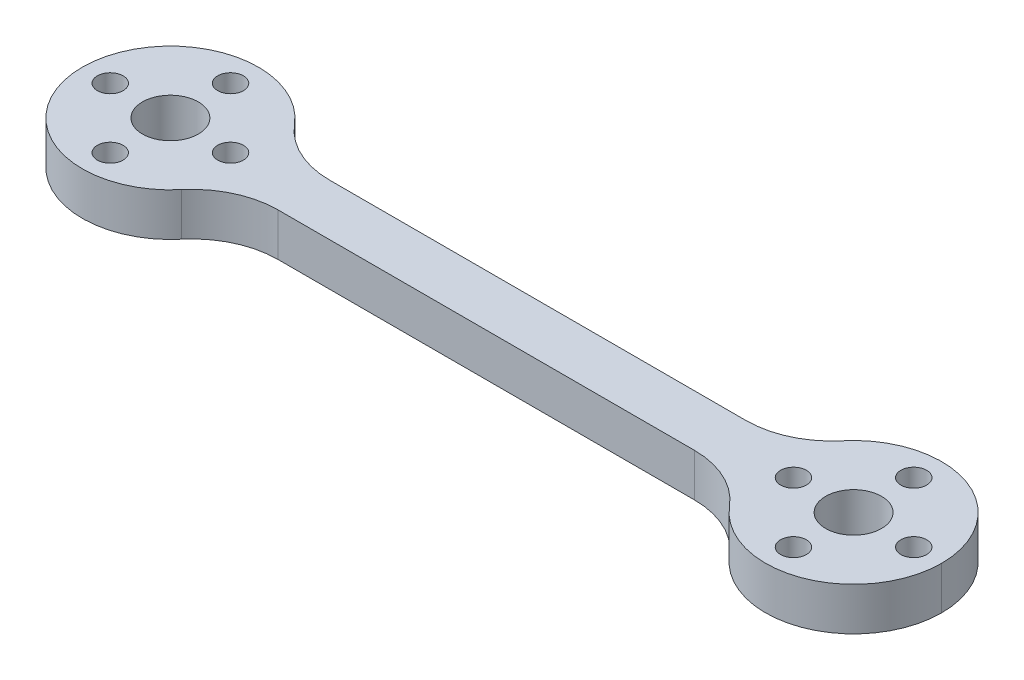
SolidWorks part; units mm, degrees
ref_plane "Front Plane" through (0, 0, 0) normal (0, 0, 1) x (1, 0, 0)
ref_plane "Top Plane" through (0, 0, 0) normal (0, 1, 0) x (1, 0, 0)
ref_plane "Right Plane" through (0, 0, 0) normal (1, 0, 0) x (0, 0, -1)
sketch "Sketch1" plane through (0, 0, 0) normal (0, 1, 0) x (1, 0, 0)
  line L0 (0, 10.25) -> (100, 10.25) construction
  line L1 (0, 0) -> (100, 0)
  line L2 (0, 0) -> (0, 20.5)
  line L3 (0, 20.5) -> (100, 20.5)
  line L4 (100, 0) -> (100, 20.5)
  line L5 (50, 20.5) -> (50, 0) construction
  line L6 (10.25, 10.25) -> (16.2336, 16.2336) construction
  line L7 (10.25, 10.25) -> (15.5852, 4.9148) construction
  circle A0 centre (10.25, 10.25) radius 3.25
  circle A1 centre (17.25, 10.25) radius 1.5
  circle A2 centre (10.25, 17.25) radius 1.5
  circle A3 centre (10.25, 3.25) radius 1.5
  circle A4 centre (3.25, 10.25) radius 1.5
  circle A5 centre (82.75, 10.25) radius 1.5
  circle A6 centre (89.75, 17.25) radius 1.5
  circle A7 centre (89.75, 3.25) radius 1.5
  circle A8 centre (96.75, 10.25) radius 1.5
  circle A9 centre (89.75, 10.25) radius 3.25
  dimension "D3" = 6.5
  dimension "D4" = 3
  dimension "D6" = 7
  dimension "D1" = 100
  dimension "D2" = 20.5
  dimension "D5" = 10.25
extrude "Boss-Extrude1" add sketch "Sketch1" along normal blind 5
fillet "Fillet1" radius 10.25 4 edges at (0, 2.5, 0) (0, 2.5, -20.5) (100, 2.5, -20.5) (100, 2.5, 0)
sketch "Sketch2" plane through (0, 5, 0) normal (0, 1, 0) x (1, 0, 0)
  line L0 (50, 20.5) -> (50, 0) construction
  line L1 (89.75, 20.5) -> (10.25, 20.5) construction
  line L2 (10.25, 0) -> (89.75, 0) construction
  line L3 (0, 10.25) -> (100, 10.25) construction
  line L4 (10.25, 20.5) -> (10.25, 10.25) construction
  line L5 (20.0511, 13.25) -> (79.9489, 13.25)
  line L6 (10.25, 20.5) -> (89.75, 20.5)
  line L7 (20.0511, 7.25) -> (79.9489, 7.25)
  line L8 (10.25, 0) -> (89.75, 0)
  arc A0 (10.25, 0) -> (20.0511, 7.25) centre (10.25, 10.25) ccw
  arc A1 (79.9489, 13.25) -> (89.75, 20.5) centre (89.75, 10.25) cw
  arc A2 (20.0511, 13.25) -> (10.25, 20.5) centre (10.25, 10.25) ccw
  arc A3 (89.75, 0) -> (79.9489, 7.25) centre (89.75, 10.25) cw
  point P24 (50, 13.25)
  point P25 (50, 7.25)
  dimension "D1" = 3
extrude "Cut-Extrude1" cut sketch "Sketch2" against normal blind 10
fillet "Fillet2" radius 10 4 edges at (79.9489, 2.5, -13.25) (79.9489, 2.5, -7.25) (20.0511, 2.5, -7.25) (20.0511, 2.5, -13.25)
